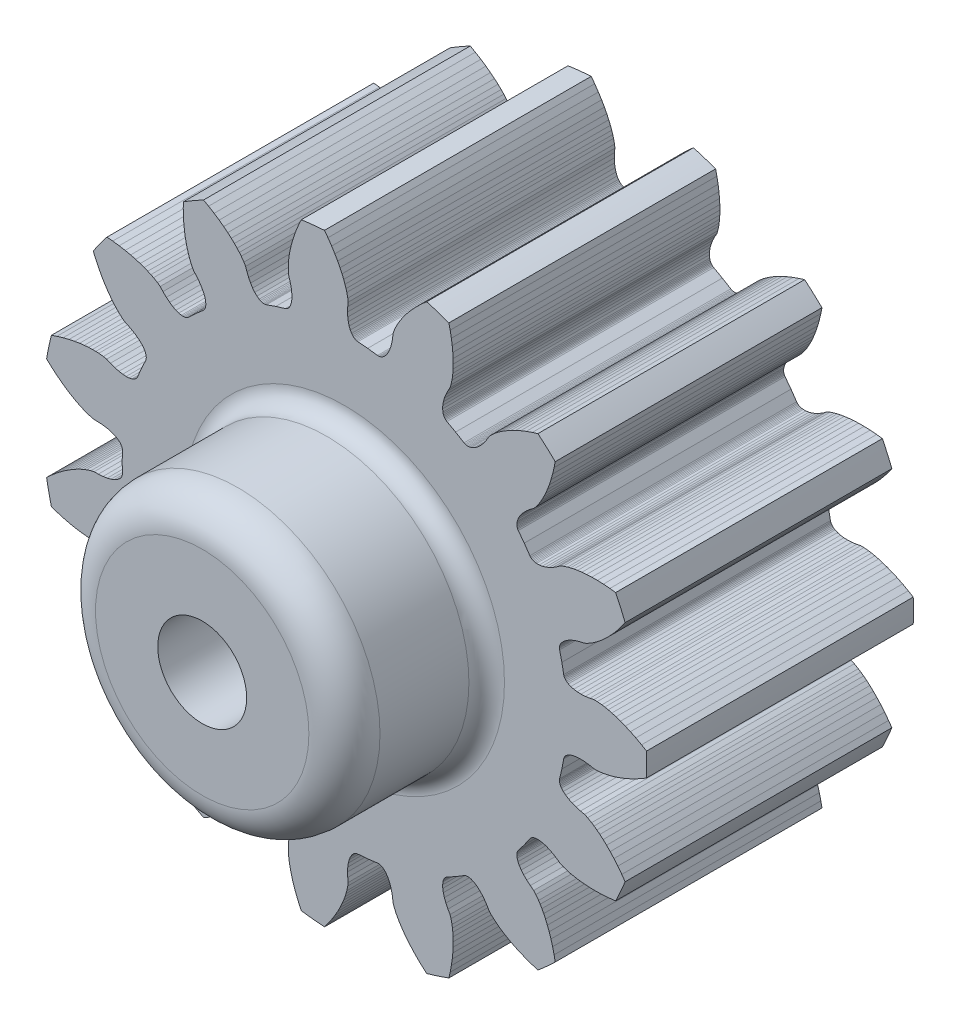
SolidWorks part; units mm, degrees
ref_plane "Front Plane" through (0, 0, 0) normal (0, 0, 1) x (1, 0, 0)
ref_plane "Top Plane" through (0, 0, 0) normal (0, 1, 0) x (1, 0, 0)
ref_plane "Right Plane" through (0, 0, 0) normal (1, 0, 0) x (0, 0, -1)
sketch "Sketch1" plane through (0, 0, 0) normal (0, 0, 1) x (1, 0, 0)
  line L0 (75.5976, 6.0436) -> (75.3755, 5.7533)
  line L1 (75.3755, 5.7533) -> (75.1578, 5.4923)
  line L2 (75.1578, 5.4923) -> (74.945, 5.2579)
  line L3 (74.945, 5.2579) -> (74.7411, 5.0514)
  line L4 (74.7411, 5.0514) -> (74.547, 4.8706)
  line L5 (74.547, 4.8706) -> (74.3629, 4.7129)
  line L6 (74.3629, 4.7129) -> (74.1941, 4.5802)
  line L7 (74.1941, 4.5802) -> (74.0385, 4.4681)
  line L8 (74.0385, 4.4681) -> (73.8985, 4.3758)
  line L9 (73.8985, 4.3758) -> (73.673, 4.2461)
  line L10 (73.673, 4.2461) -> (73.5054, 4.1687)
  line L11 (73.5054, 4.1687) -> (73.2759, 4.1194)
  line L12 (73.2759, 4.1194) -> (73.0228, 4.0472)
  line L13 (73.0228, 4.0472) -> (72.7991, 3.9621)
  line L14 (72.7991, 3.9621) -> (72.6055, 3.8665)
  line L15 (72.6055, 3.8665) -> (72.4424, 3.7627)
  line L16 (72.4424, 3.7627) -> (72.3101, 3.6532)
  line L17 (72.3101, 3.6532) -> (72.2087, 3.5403)
  line L18 (72.2087, 3.5403) -> (72.1697, 3.4833)
  line L19 (72.1697, 3.4833) -> (72.1383, 3.4264)
  line L20 (72.1383, 3.4264) -> (72.1147, 3.3698)
  line L21 (72.1147, 3.3698) -> (72.0987, 3.3139)
  line L22 (72.0987, 3.3139) -> (72.0903, 3.2589)
  line L23 (72.0903, 3.2589) -> (72.0896, 3.2051)
  line L24 (72.0896, 3.2051) -> (72.0992, 3.1402)
  line L25 (72.0992, 3.1402) -> (72.2268, 2.5989)
  line L26 (72.2268, 2.5989) -> (72.3304, 2.0525)
  line L27 (72.3304, 2.0525) -> (72.348, 1.9892)
  line L28 (72.348, 1.9892) -> (72.3706, 1.9404)
  line L29 (72.3706, 1.9404) -> (72.4006, 1.8936)
  line L30 (72.4006, 1.8936) -> (72.4379, 1.849)
  line L31 (72.4379, 1.849) -> (72.4825, 1.807)
  line L32 (72.4825, 1.807) -> (72.5343, 1.7677)
  line L33 (72.5343, 1.7677) -> (72.5932, 1.7315)
  line L34 (72.5932, 1.7315) -> (72.7317, 1.6696)
  line L35 (72.7317, 1.6696) -> (72.8972, 1.6234)
  line L36 (72.8972, 1.6234) -> (73.0884, 1.5949)
  line L37 (73.0884, 1.5949) -> (73.3041, 1.5863)
  line L38 (73.3041, 1.5863) -> (73.543, 1.5995)
  line L39 (73.543, 1.5995) -> (73.8036, 1.6365)
  line L40 (73.8036, 1.6365) -> (74.0333, 1.6849)
  line L41 (74.0333, 1.6849) -> (74.218, 1.6823)
  line L42 (74.218, 1.6823) -> (74.4767, 1.6556)
  line L43 (74.4767, 1.6556) -> (74.6422, 1.6282)
  line L44 (74.6422, 1.6282) -> (74.8299, 1.589)
  line L45 (74.8299, 1.589) -> (75.0381, 1.5364)
  line L46 (75.0381, 1.5364) -> (75.2704, 1.4673)
  line L47 (75.2704, 1.4673) -> (75.5213, 1.3811)
  line L48 (75.5213, 1.3811) -> (75.7915, 1.2753)
  line L49 (75.7915, 1.2753) -> (76.0812, 1.1478)
  line L50 (76.0812, 1.1478) -> (76.3863, 0.9979)
  line L51 (76.3863, 0.9979) -> (76.7073, 0.8231)
  line L52 (76.7073, 0.8231) -> (76.9873, 0.656)
  line L53 (76.9873, -0.656) -> (76.7073, -0.8231)
  line L54 (76.7073, -0.8231) -> (76.3863, -0.9979)
  line L55 (76.3863, -0.9979) -> (76.0812, -1.1478)
  line L56 (76.0812, -1.1478) -> (75.7915, -1.2753)
  line L57 (75.7915, -1.2753) -> (75.5213, -1.3811)
  line L58 (75.5213, -1.3811) -> (75.2704, -1.4673)
  line L59 (75.2704, -1.4673) -> (75.0381, -1.5364)
  line L60 (75.0381, -1.5364) -> (74.8299, -1.589)
  line L61 (74.8299, -1.589) -> (74.6422, -1.6282)
  line L62 (74.6422, -1.6282) -> (74.4767, -1.6556)
  line L63 (74.4767, -1.6556) -> (74.218, -1.6823)
  line L64 (74.218, -1.6823) -> (74.0333, -1.6849)
  line L65 (74.0333, -1.6849) -> (73.8036, -1.6365)
  line L66 (73.8036, -1.6365) -> (73.543, -1.5995)
  line L67 (73.543, -1.5995) -> (73.3041, -1.5863)
  line L68 (73.3041, -1.5863) -> (73.0884, -1.5949)
  line L69 (73.0884, -1.5949) -> (72.8972, -1.6234)
  line L70 (72.8972, -1.6234) -> (72.7317, -1.6696)
  line L71 (72.7317, -1.6696) -> (72.5932, -1.7315)
  line L72 (72.5932, -1.7315) -> (72.5343, -1.7677)
  line L73 (72.5343, -1.7677) -> (72.4825, -1.807)
  line L74 (72.4825, -1.807) -> (72.4379, -1.849)
  line L75 (72.4379, -1.849) -> (72.4006, -1.8936)
  line L76 (72.4006, -1.8936) -> (72.3706, -1.9404)
  line L77 (72.3706, -1.9404) -> (72.348, -1.9892)
  line L78 (72.348, -1.9892) -> (72.3304, -2.0525)
  line L79 (72.3304, -2.0525) -> (72.2268, -2.5989)
  line L80 (72.2268, -2.5989) -> (72.0992, -3.1402)
  line L81 (72.0992, -3.1402) -> (72.0896, -3.2051)
  line L82 (72.0896, -3.2051) -> (72.0903, -3.2589)
  line L83 (72.0903, -3.2589) -> (72.0987, -3.3139)
  line L84 (72.0987, -3.3139) -> (72.1147, -3.3698)
  line L85 (72.1147, -3.3698) -> (72.1383, -3.4264)
  line L86 (72.1383, -3.4264) -> (72.1697, -3.4833)
  line L87 (72.1697, -3.4833) -> (72.2087, -3.5403)
  line L88 (72.2087, -3.5403) -> (72.3101, -3.6532)
  line L89 (72.3101, -3.6532) -> (72.4424, -3.7627)
  line L90 (72.4424, -3.7627) -> (72.6055, -3.8665)
  line L91 (72.6055, -3.8665) -> (72.7991, -3.9621)
  line L92 (72.7991, -3.9621) -> (73.0228, -4.0472)
  line L93 (73.0228, -4.0472) -> (73.2759, -4.1194)
  line L94 (73.2759, -4.1194) -> (73.5054, -4.1687)
  line L95 (73.5054, -4.1687) -> (73.673, -4.2461)
  line L96 (73.673, -4.2461) -> (73.8985, -4.3758)
  line L97 (73.8985, -4.3758) -> (74.0385, -4.4681)
  line L98 (74.0385, -4.4681) -> (74.1941, -4.5802)
  line L99 (74.1941, -4.5802) -> (74.3629, -4.7129)
  line L100 (74.3629, -4.7129) -> (74.547, -4.8706)
  line L101 (74.547, -4.8706) -> (74.7411, -5.0514)
  line L102 (74.7411, -5.0514) -> (74.945, -5.2579)
  line L103 (74.945, -5.2579) -> (75.1578, -5.4923)
  line L104 (75.1578, -5.4923) -> (75.3755, -5.7533)
  line L105 (75.3755, -5.7533) -> (75.5976, -6.0436)
  line L106 (75.5976, -6.0436) -> (75.7855, -6.3101)
  line L107 (75.2519, -7.5086) -> (74.9281, -7.5474)
  line L108 (74.9281, -7.5474) -> (74.5638, -7.5765)
  line L109 (74.5638, -7.5765) -> (74.2241, -7.5894)
  line L110 (74.2241, -7.5894) -> (73.9075, -7.5881)
  line L111 (73.9075, -7.5881) -> (73.6176, -7.5747)
  line L112 (73.6176, -7.5747) -> (73.3534, -7.5515)
  line L113 (73.3534, -7.5515) -> (73.1131, -7.5202)
  line L114 (73.1131, -7.5202) -> (72.9015, -7.4835)
  line L115 (72.9015, -7.4835) -> (72.714, -7.443)
  line L116 (72.714, -7.443) -> (72.5518, -7.4007)
  line L117 (72.5518, -7.4007) -> (72.3045, -7.3199)
  line L118 (72.3045, -7.3199) -> (72.1348, -7.2471)
  line L119 (72.1348, -7.2471) -> (71.9446, -7.1095)
  line L120 (71.9446, -7.1095) -> (71.7216, -6.9697)
  line L121 (71.7216, -6.9697) -> (71.5087, -6.8604)
  line L122 (71.5087, -6.8604) -> (71.3081, -6.7805)
  line L123 (71.3081, -6.7805) -> (71.1219, -6.7288)
  line L124 (71.1219, -6.7288) -> (70.9519, -6.7037)
  line L125 (70.9519, -6.7037) -> (70.8002, -6.704)
  line L126 (70.8002, -6.704) -> (70.7317, -6.713)
  line L127 (70.7317, -6.713) -> (70.6684, -6.7278)
  line L128 (70.6684, -6.7278) -> (70.6105, -6.7481)
  line L129 (70.6105, -6.7481) -> (70.5583, -6.7737)
  line L130 (70.5583, -6.7737) -> (70.5118, -6.8043)
  line L131 (70.5118, -6.8043) -> (70.4714, -6.8396)
  line L132 (70.4714, -6.8396) -> (70.4295, -6.8903)
  line L133 (70.4295, -6.8903) -> (70.1127, -7.3473)
  line L134 (70.1127, -7.3473) -> (69.7759, -7.7899)
  line L135 (69.7759, -7.7899) -> (69.7407, -7.8453)
  line L136 (69.7407, -7.8453) -> (69.7196, -7.8947)
  line L137 (69.7196, -7.8947) -> (69.7048, -7.9484)
  line L138 (69.7048, -7.9484) -> (69.6967, -8.0059)
  line L139 (69.6967, -8.0059) -> (69.6953, -8.0672)
  line L140 (69.6953, -8.0672) -> (69.7008, -8.132)
  line L141 (69.7008, -8.132) -> (69.7133, -8.2)
  line L142 (69.7133, -8.2) -> (69.76, -8.3443)
  line L143 (69.76, -8.3443) -> (69.8363, -8.4982)
  line L144 (69.8363, -8.4982) -> (69.9431, -8.6594)
  line L145 (69.9431, -8.6594) -> (70.081, -8.8254)
  line L146 (70.081, -8.8254) -> (70.2507, -8.9941)
  line L147 (70.2507, -8.9941) -> (70.4526, -9.163)
  line L148 (70.4526, -9.163) -> (70.6422, -9.3014)
  line L149 (70.6422, -9.3014) -> (70.7639, -9.4403)
  line L150 (70.7639, -9.4403) -> (70.9172, -9.6505)
  line L151 (70.9172, -9.6505) -> (71.0075, -9.7918)
  line L152 (71.0075, -9.7918) -> (71.104, -9.9575)
  line L153 (71.104, -9.9575) -> (71.2043, -10.1474)
  line L154 (71.2043, -10.1474) -> (71.3083, -10.3663)
  line L155 (71.3083, -10.3663) -> (71.4121, -10.6104)
  line L156 (71.4121, -10.6104) -> (71.5144, -10.882)
  line L157 (71.5144, -10.882) -> (71.6134, -11.1827)
  line L158 (71.6134, -11.1827) -> (71.7061, -11.5097)
  line L159 (71.7061, -11.5097) -> (71.791, -11.8652)
  line L160 (71.791, -11.8652) -> (71.8542, -12.1851)
  line L161 (70.8792, -13.063) -> (70.5677, -12.9667)
  line L162 (70.5677, -12.9667) -> (70.223, -12.8451)
  line L163 (70.223, -12.8451) -> (69.9075, -12.7187)
  line L164 (69.9075, -12.7187) -> (69.6188, -12.5888)
  line L165 (69.6188, -12.5888) -> (69.3594, -12.4587)
  line L166 (69.3594, -12.4587) -> (69.1275, -12.33)
  line L167 (69.1275, -12.33) -> (68.9207, -12.2036)
  line L168 (68.9207, -12.2036) -> (68.7423, -12.0841)
  line L169 (68.7423, -12.0841) -> (68.5875, -11.9707)
  line L170 (68.5875, -11.9707) -> (68.4565, -11.8661)
  line L171 (68.4565, -11.8661) -> (68.2635, -11.6917)
  line L172 (68.2635, -11.6917) -> (68.138, -11.5562)
  line L173 (68.138, -11.5562) -> (68.0202, -11.3531)
  line L174 (68.0202, -11.3531) -> (67.8734, -11.1347)
  line L175 (67.8734, -11.1347) -> (67.7233, -10.9483)
  line L176 (67.7233, -10.9483) -> (67.5726, -10.7938)
  line L177 (67.5726, -10.7938) -> (67.4235, -10.6707)
  line L178 (67.4235, -10.6707) -> (67.2784, -10.5787)
  line L179 (67.2784, -10.5787) -> (67.1397, -10.5172)
  line L180 (67.1397, -10.5172) -> (67.0735, -10.4976)
  line L181 (67.0735, -10.4976) -> (67.0096, -10.4854)
  line L182 (67.0096, -10.4854) -> (66.9485, -10.4804)
  line L183 (66.9485, -10.4804) -> (66.8904, -10.4825)
  line L184 (66.8904, -10.4825) -> (66.8355, -10.4915)
  line L185 (66.8355, -10.4915) -> (66.7842, -10.5074)
  line L186 (66.7842, -10.5074) -> (66.7253, -10.5367)
  line L187 (66.7253, -10.5367) -> (66.25, -10.8253)
  line L188 (66.25, -10.8253) -> (65.7624, -11.0926)
  line L189 (65.7624, -11.0926) -> (65.7076, -11.129)
  line L190 (65.7076, -11.129) -> (65.6682, -11.1655)
  line L191 (65.6682, -11.1655) -> (65.6329, -11.2085)
  line L192 (65.6329, -11.2085) -> (65.602, -11.2578)
  line L193 (65.602, -11.2578) -> (65.5758, -11.3132)
  line L194 (65.5758, -11.3132) -> (65.5545, -11.3746)
  line L195 (65.5545, -11.3746) -> (65.5383, -11.4418)
  line L196 (65.5383, -11.4418) -> (65.5222, -11.5927)
  line L197 (65.5222, -11.5927) -> (65.5293, -11.7643)
  line L198 (65.5293, -11.7643) -> (65.5614, -11.9549)
  line L199 (65.5614, -11.9549) -> (65.6199, -12.1628)
  line L200 (65.6199, -12.1628) -> (65.7063, -12.3859)
  line L201 (65.7063, -12.3859) -> (65.822, -12.6223)
  line L202 (65.822, -12.6223) -> (65.9389, -12.8259)
  line L203 (65.9389, -12.8259) -> (65.9936, -13.0022)
  line L204 (65.9936, -13.0022) -> (66.0481, -13.2566)
  line L205 (66.0481, -13.2566) -> (66.0732, -13.4224)
  line L206 (66.0732, -13.4224) -> (66.094, -13.6131)
  line L207 (66.094, -13.6131) -> (66.1083, -13.8273)
  line L208 (66.1083, -13.8273) -> (66.1143, -14.0696)
  line L209 (66.1143, -14.0696) -> (66.1098, -14.3348)
  line L210 (66.1098, -14.3348) -> (66.0928, -14.6245)
  line L211 (66.0928, -14.6245) -> (66.061, -14.9395)
  line L212 (66.061, -14.9395) -> (66.0127, -15.2759)
  line L213 (66.0127, -15.2759) -> (65.9456, -15.6352)
  line L214 (65.9456, -15.6352) -> (65.8732, -15.9532)
  line L215 (64.6255, -16.3586) -> (64.3801, -16.1439)
  line L216 (64.3801, -16.1439) -> (64.1146, -15.8926)
  line L217 (64.1146, -15.8926) -> (63.8778, -15.6488)
  line L218 (63.8778, -15.6488) -> (63.6669, -15.4127)
  line L219 (63.6669, -15.4127) -> (63.4829, -15.1884)
  line L220 (63.4829, -15.1884) -> (63.3233, -14.9765)
  line L221 (63.3233, -14.9765) -> (63.1858, -14.7769)
  line L222 (63.1858, -14.7769) -> (63.0715, -14.5951)
  line L223 (63.0715, -14.5951) -> (62.9762, -14.4287)
  line L224 (62.9762, -14.4287) -> (62.899, -14.2798)
  line L225 (62.899, -14.2798) -> (62.7936, -14.042)
  line L226 (62.7936, -14.042) -> (62.7341, -13.8671)
  line L227 (62.7341, -13.8671) -> (62.7091, -13.6337)
  line L228 (62.7091, -13.6337) -> (62.6638, -13.3745)
  line L229 (62.6638, -13.3745) -> (62.6025, -13.1432)
  line L230 (62.6025, -13.1432) -> (62.5277, -12.9406)
  line L231 (62.5277, -12.9406) -> (62.4415, -12.7676)
  line L232 (62.4415, -12.7676) -> (62.3464, -12.6246)
  line L233 (62.3464, -12.6246) -> (62.2447, -12.5119)
  line L234 (62.2447, -12.5119) -> (62.1921, -12.4671)
  line L235 (62.1921, -12.4671) -> (62.1388, -12.43)
  line L236 (62.1388, -12.43) -> (62.085, -12.4005)
  line L237 (62.085, -12.4005) -> (62.0311, -12.3788)
  line L238 (62.0311, -12.3788) -> (61.9773, -12.3648)
  line L239 (61.9773, -12.3648) -> (61.9239, -12.3584)
  line L240 (61.9239, -12.3584) -> (61.8582, -12.3611)
  line L241 (61.8582, -12.3611) -> (61.3066, -12.4315)
  line L242 (61.3066, -12.4315) -> (60.7524, -12.4774)
  line L243 (60.7524, -12.4774) -> (60.6876, -12.4883)
  line L244 (60.6876, -12.4883) -> (60.6367, -12.5057)
  line L245 (60.6367, -12.5057) -> (60.587, -12.5306)
  line L246 (60.587, -12.5306) -> (60.5388, -12.5631)
  line L247 (60.5388, -12.5631) -> (60.4923, -12.603)
  line L248 (60.4923, -12.603) -> (60.4478, -12.6504)
  line L249 (60.4478, -12.6504) -> (60.4057, -12.7052)
  line L250 (60.4057, -12.7052) -> (60.3296, -12.8365)
  line L251 (60.3296, -12.8365) -> (60.2663, -12.9962)
  line L252 (60.2663, -12.9962) -> (60.2181, -13.1834)
  line L253 (60.2181, -13.1834) -> (60.1869, -13.397)
  line L254 (60.1869, -13.397) -> (60.1751, -13.636)
  line L255 (60.1751, -13.636) -> (60.1847, -13.8991)
  line L256 (60.1847, -13.8991) -> (60.2087, -14.1326)
  line L257 (60.2087, -14.1326) -> (60.1869, -14.316)
  line L258 (60.1869, -14.316) -> (60.1333, -14.5705)
  line L259 (60.1333, -14.5705) -> (60.0888, -14.7321)
  line L260 (60.0888, -14.7321) -> (60.0302, -14.9148)
  line L261 (60.0302, -14.9148) -> (59.9561, -15.1163)
  line L262 (59.9561, -15.1163) -> (59.8631, -15.3401)
  line L263 (59.8631, -15.3401) -> (59.7511, -15.5806)
  line L264 (59.7511, -15.5806) -> (59.6177, -15.8383)
  line L265 (59.6177, -15.8383) -> (59.4605, -16.1131)
  line L266 (59.4605, -16.1131) -> (59.2796, -16.4008)
  line L267 (59.2796, -16.4008) -> (59.0722, -16.7018)
  line L268 (59.0722, -16.7018) -> (58.8767, -16.9628)
  line L269 (57.572, -16.8257) -> (57.4351, -16.5297)
  line L270 (57.4351, -16.5297) -> (57.2948, -16.1922)
  line L271 (57.2948, -16.1922) -> (57.1776, -15.8731)
  line L272 (57.1776, -15.8731) -> (57.081, -15.5717)
  line L273 (57.081, -15.5717) -> (57.0041, -15.2919)
  line L274 (57.0041, -15.2919) -> (56.9445, -15.0334)
  line L275 (56.9445, -15.0334) -> (56.9001, -14.7951)
  line L276 (56.9001, -14.7951) -> (56.8695, -14.5826)
  line L277 (56.8695, -14.5826) -> (56.8502, -14.3918)
  line L278 (56.8502, -14.3918) -> (56.8403, -14.2244)
  line L279 (56.8403, -14.2244) -> (56.8407, -13.9642)
  line L280 (56.8407, -13.9642) -> (56.8575, -13.7804)
  line L281 (56.8575, -13.7804) -> (56.9296, -13.5569)
  line L282 (56.9296, -13.5569) -> (56.9936, -13.3016)
  line L283 (56.9936, -13.3016) -> (57.0317, -13.0654)
  line L284 (57.0317, -13.0654) -> (57.0457, -12.85)
  line L285 (57.0457, -12.85) -> (57.0374, -12.6568)
  line L286 (57.0374, -12.6568) -> (57.0087, -12.4875)
  line L287 (57.0087, -12.4875) -> (56.9616, -12.3432)
  line L288 (56.9616, -12.3432) -> (56.9318, -12.2809)
  line L289 (56.9318, -12.2809) -> (56.8982, -12.2253)
  line L290 (56.8982, -12.2253) -> (56.861, -12.1765)
  line L291 (56.861, -12.1765) -> (56.8206, -12.1347)
  line L292 (56.8206, -12.1347) -> (56.7771, -12.1)
  line L293 (56.7771, -12.1) -> (56.7309, -12.0725)
  line L294 (56.7309, -12.0725) -> (56.6699, -12.0483)
  line L295 (56.6699, -12.0483) -> (56.1373, -11.8882)
  line L296 (56.1373, -11.8882) -> (55.6123, -11.7047)
  line L297 (55.6123, -11.7047) -> (55.5487, -11.6883)
  line L298 (55.5487, -11.6883) -> (55.4952, -11.6835)
  line L299 (55.4952, -11.6835) -> (55.4396, -11.686)
  line L300 (55.4396, -11.686) -> (55.3823, -11.6961)
  line L301 (55.3823, -11.6961) -> (55.3236, -11.7137)
  line L302 (55.3236, -11.7137) -> (55.2637, -11.7389)
  line L303 (55.2637, -11.7389) -> (55.2029, -11.7718)
  line L304 (55.2029, -11.7718) -> (55.0801, -11.8608)
  line L305 (55.0801, -11.8608) -> (54.9573, -11.981)
  line L306 (54.9573, -11.981) -> (54.837, -12.1323)
  line L307 (54.837, -12.1323) -> (54.7217, -12.3149)
  line L308 (54.7217, -12.3149) -> (54.6137, -12.5284)
  line L309 (54.6137, -12.5284) -> (54.5155, -12.7725)
  line L310 (54.5155, -12.7725) -> (54.4425, -12.9957)
  line L311 (54.4425, -12.9957) -> (54.348, -13.1543)
  line L312 (54.348, -13.1543) -> (54.1954, -13.365)
  line L313 (54.1954, -13.365) -> (54.089, -13.4946)
  line L314 (54.089, -13.4946) -> (53.9612, -13.6376)
  line L315 (53.9612, -13.6376) -> (53.8115, -13.7916)
  line L316 (53.8115, -13.7916) -> (53.6355, -13.9582)
  line L317 (53.6355, -13.9582) -> (53.4354, -14.1323)
  line L318 (53.4354, -14.1323) -> (53.2087, -14.3135)
  line L319 (53.2087, -14.3135) -> (52.9534, -14.5006)
  line L320 (52.9534, -14.5006) -> (52.671, -14.6899)
  line L321 (52.671, -14.6899) -> (52.3592, -14.8805)
  line L322 (52.3592, -14.8805) -> (52.0744, -15.0394)
  line L323 (50.9383, -14.3834) -> (50.9336, -14.0574)
  line L324 (50.9336, -14.0574) -> (50.9427, -13.692)
  line L325 (50.9427, -13.692) -> (50.9654, -13.3528)
  line L326 (50.9654, -13.3528) -> (50.9998, -13.0382)
  line L327 (50.9998, -13.0382) -> (51.0433, -12.7513)
  line L328 (51.0433, -12.7513) -> (51.0941, -12.4909)
  line L329 (51.0941, -12.4909) -> (51.1504, -12.2552)
  line L330 (51.1504, -12.2552) -> (51.2089, -12.0486)
  line L331 (51.2089, -12.0486) -> (51.2688, -11.8664)
  line L332 (51.2688, -11.8664) -> (51.3279, -11.7094)
  line L333 (51.3279, -11.7094) -> (51.4341, -11.472)
  line L334 (51.4341, -11.472) -> (51.5242, -11.3108)
  line L335 (51.5242, -11.3108) -> (51.6809, -11.136)
  line L336 (51.6809, -11.136) -> (51.8432, -10.9288)
  line L337 (51.8432, -10.9288) -> (51.9742, -10.7286)
  line L338 (51.9742, -10.7286) -> (52.0746, -10.5374)
  line L339 (52.0746, -10.5374) -> (52.1455, -10.3576)
  line L340 (52.1455, -10.3576) -> (52.1882, -10.1912)
  line L341 (52.1882, -10.1912) -> (52.2038, -10.0403)
  line L342 (52.2038, -10.0403) -> (52.202, -9.9712)
  line L343 (52.202, -9.9712) -> (52.1939, -9.9067)
  line L344 (52.1939, -9.9067) -> (52.1797, -9.847)
  line L345 (52.1797, -9.847) -> (52.1598, -9.7924)
  line L346 (52.1598, -9.7924) -> (52.1342, -9.743)
  line L347 (52.1342, -9.743) -> (52.1033, -9.6991)
  line L348 (52.1033, -9.6991) -> (52.0573, -9.6522)
  line L349 (52.0573, -9.6522) -> (51.6359, -9.2893)
  line L350 (51.6359, -9.2893) -> (51.231, -8.9081)
  line L351 (51.231, -8.9081) -> (51.1795, -8.8673)
  line L352 (51.1795, -8.8673) -> (51.1325, -8.8411)
  line L353 (51.1325, -8.8411) -> (51.0808, -8.8208)
  line L354 (51.0808, -8.8208) -> (51.0243, -8.8067)
  line L355 (51.0243, -8.8067) -> (50.9635, -8.7989)
  line L356 (50.9635, -8.7989) -> (50.8985, -8.7976)
  line L357 (50.8985, -8.7976) -> (50.8297, -8.8029)
  line L358 (50.8297, -8.8029) -> (50.6812, -8.8343)
  line L359 (50.6812, -8.8343) -> (50.5202, -8.8941)
  line L360 (50.5202, -8.8941) -> (50.3487, -8.9835)
  line L361 (50.3487, -8.9835) -> (50.1691, -9.1033)
  line L362 (50.1691, -9.1033) -> (49.9836, -9.2544)
  line L363 (49.9836, -9.2544) -> (49.7946, -9.4375)
  line L364 (49.7946, -9.4375) -> (49.6371, -9.6117)
  line L365 (49.6371, -9.6117) -> (49.4863, -9.7182)
  line L366 (49.4863, -9.7182) -> (49.2612, -9.8486)
  line L367 (49.2612, -9.8486) -> (49.1113, -9.9237)
  line L368 (49.1113, -9.9237) -> (48.9363, -10.0024)
  line L369 (48.9363, -10.0024) -> (48.737, -10.0822)
  line L370 (48.737, -10.0822) -> (48.5084, -10.1628)
  line L371 (48.5084, -10.1628) -> (48.2548, -10.2405)
  line L372 (48.2548, -10.2405) -> (47.974, -10.3138)
  line L373 (47.974, -10.3138) -> (47.6647, -10.3809)
  line L374 (47.6647, -10.3809) -> (47.3297, -10.4389)
  line L375 (47.3297, -10.4389) -> (46.9673, -10.4862)
  line L376 (46.9673, -10.4862) -> (46.6426, -10.5156)
  line L377 (45.8714, -9.4542) -> (45.9997, -9.1544)
  line L378 (45.9997, -9.1544) -> (46.1567, -8.8243)
  line L379 (46.1567, -8.8243) -> (46.3154, -8.5237)
  line L380 (46.3154, -8.5237) -> (46.4748, -8.2502)
  line L381 (46.4748, -8.2502) -> (46.6313, -8.0059)
  line L382 (46.6313, -8.0059) -> (46.7835, -7.7886)
  line L383 (46.7835, -7.7886) -> (46.9308, -7.5962)
  line L384 (46.9308, -7.5962) -> (47.0683, -7.4313)
  line L385 (47.0683, -7.4313) -> (47.1972, -7.2892)
  line L386 (47.1972, -7.2892) -> (47.315, -7.1698)
  line L387 (47.315, -7.1698) -> (47.5086, -6.9961)
  line L388 (47.5086, -6.9961) -> (47.6565, -6.8855)
  line L389 (47.6565, -6.8855) -> (47.8707, -6.7896)
  line L390 (47.8707, -6.7896) -> (48.1033, -6.6663)
  line L391 (48.1033, -6.6663) -> (48.3043, -6.5366)
  line L392 (48.3043, -6.5366) -> (48.4738, -6.4029)
  line L393 (48.4738, -6.4029) -> (48.6118, -6.2674)
  line L394 (48.6118, -6.2674) -> (48.7184, -6.1328)
  line L395 (48.7184, -6.1328) -> (48.7941, -6.0013)
  line L396 (48.7941, -6.0013) -> (48.8205, -5.9374)
  line L397 (48.8205, -5.9374) -> (48.8393, -5.8752)
  line L398 (48.8393, -5.8752) -> (48.8507, -5.8149)
  line L399 (48.8507, -5.8149) -> (48.8547, -5.7569)
  line L400 (48.8547, -5.7569) -> (48.8514, -5.7014)
  line L401 (48.8514, -5.7014) -> (48.841, -5.6487)
  line L402 (48.841, -5.6487) -> (48.8181, -5.5871)
  line L403 (48.8181, -5.5871) -> (48.5807, -5.0842)
  line L404 (48.5807, -5.0842) -> (48.3658, -4.5713)
  line L405 (48.3658, -4.5713) -> (48.3354, -4.5131)
  line L406 (48.3354, -4.5131) -> (48.3032, -4.47)
  line L407 (48.3032, -4.47) -> (48.2641, -4.4305)
  line L408 (48.2641, -4.4305) -> (48.2183, -4.3946)
  line L409 (48.2183, -4.3946) -> (48.1659, -4.3627)
  line L410 (48.1659, -4.3627) -> (48.1071, -4.3351)
  line L411 (48.1071, -4.3351) -> (48.042, -4.312)
  line L412 (48.042, -4.312) -> (47.8936, -4.2802)
  line L413 (47.8936, -4.2802) -> (47.7222, -4.2694)
  line L414 (47.7222, -4.2694) -> (47.5292, -4.2813)
  line L415 (47.5292, -4.2813) -> (47.3164, -4.3177)
  line L416 (47.3164, -4.3177) -> (47.0855, -4.3803)
  line L417 (47.0855, -4.3803) -> (46.8383, -4.4707)
  line L418 (46.8383, -4.4707) -> (46.6236, -4.5657)
  line L419 (46.6236, -4.5657) -> (46.4425, -4.6017)
  line L420 (46.4425, -4.6017) -> (46.1838, -4.6293)
  line L421 (46.1838, -4.6293) -> (46.0163, -4.6369)
  line L422 (46.0163, -4.6369) -> (45.8245, -4.6376)
  line L423 (45.8245, -4.6376) -> (45.6099, -4.6295)
  line L424 (45.6099, -4.6295) -> (45.3684, -4.6101)
  line L425 (45.3684, -4.6101) -> (45.1051, -4.5779)
  line L426 (45.1051, -4.5779) -> (44.8187, -4.5307)
  line L427 (44.8187, -4.5307) -> (44.5088, -4.4662)
  line L428 (44.5088, -4.4662) -> (44.1793, -4.3829)
  line L429 (44.1793, -4.3829) -> (43.8289, -4.2787)
  line L430 (43.8289, -4.2787) -> (43.5203, -4.1735)
  line L431 (43.2475, -2.8902) -> (43.4867, -2.6686)
  line L432 (43.4867, -2.6686) -> (43.7643, -2.4308)
  line L433 (43.7643, -2.4308) -> (44.0316, -2.2208)
  line L434 (44.0316, -2.2208) -> (44.2884, -2.0358)
  line L435 (44.2884, -2.0358) -> (44.5308, -1.8762)
  line L436 (44.5308, -1.8762) -> (44.7582, -1.7396)
  line L437 (44.7582, -1.7396) -> (44.9711, -1.6237)
  line L438 (44.9711, -1.6237) -> (45.1638, -1.529)
  line L439 (45.1638, -1.529) -> (45.3393, -1.4516)
  line L440 (45.3393, -1.4516) -> (45.4954, -1.3905)
  line L441 (45.4954, -1.3905) -> (45.7429, -1.3105)
  line L442 (45.7429, -1.3105) -> (45.923, -1.2697)
  line L443 (45.923, -1.2697) -> (46.1578, -1.2692)
  line L444 (46.1578, -1.2692) -> (46.4204, -1.2512)
  line L445 (46.4204, -1.2512) -> (46.6568, -1.2145)
  line L446 (46.6568, -1.2145) -> (46.866, -1.1612)
  line L447 (46.866, -1.1612) -> (47.0472, -1.0936)
  line L448 (47.0472, -1.0936) -> (47.1993, -1.0139)
  line L449 (47.1993, -1.0139) -> (47.322, -0.9246)
  line L450 (47.322, -0.9246) -> (47.3721, -0.877)
  line L451 (47.3721, -0.877) -> (47.4145, -0.8278)
  line L452 (47.4145, -0.8278) -> (47.4494, -0.7774)
  line L453 (47.4494, -0.7774) -> (47.4767, -0.726)
  line L454 (47.4767, -0.726) -> (47.4963, -0.674)
  line L455 (47.4963, -0.674) -> (47.5082, -0.6215)
  line L456 (47.5082, -0.6215) -> (47.5123, -0.556)
  line L457 (47.5123, -0.556) -> (47.5, 0)
  line L458 (47.5, 0) -> (47.5123, 0.556)
  line L459 (47.5123, 0.556) -> (47.5082, 0.6215)
  line L460 (47.5082, 0.6215) -> (47.4963, 0.674)
  line L461 (47.4963, 0.674) -> (47.4767, 0.726)
  line L462 (47.4767, 0.726) -> (47.4494, 0.7774)
  line L463 (47.4494, 0.7774) -> (47.4145, 0.8278)
  line L464 (47.4145, 0.8278) -> (47.3721, 0.877)
  line L465 (47.3721, 0.877) -> (47.322, 0.9246)
  line L466 (47.322, 0.9246) -> (47.1993, 1.0139)
  line L467 (47.1993, 1.0139) -> (47.0472, 1.0936)
  line L468 (47.0472, 1.0936) -> (46.866, 1.1612)
  line L469 (46.866, 1.1612) -> (46.6568, 1.2145)
  line L470 (46.6568, 1.2145) -> (46.4204, 1.2512)
  line L471 (46.4204, 1.2512) -> (46.1578, 1.2692)
  line L472 (46.1578, 1.2692) -> (45.923, 1.2697)
  line L473 (45.923, 1.2697) -> (45.7429, 1.3105)
  line L474 (45.7429, 1.3105) -> (45.4954, 1.3905)
  line L475 (45.4954, 1.3905) -> (45.3393, 1.4516)
  line L476 (45.3393, 1.4516) -> (45.1638, 1.529)
  line L477 (45.1638, 1.529) -> (44.9711, 1.6237)
  line L478 (44.9711, 1.6237) -> (44.7582, 1.7396)
  line L479 (44.7582, 1.7396) -> (44.5308, 1.8762)
  line L480 (44.5308, 1.8762) -> (44.2884, 2.0358)
  line L481 (44.2884, 2.0358) -> (44.0316, 2.2208)
  line L482 (44.0316, 2.2208) -> (43.7643, 2.4308)
  line L483 (43.7643, 2.4308) -> (43.4867, 2.6686)
  line L484 (43.4867, 2.6686) -> (43.2475, 2.8902)
  line L485 (43.5203, 4.1735) -> (43.8289, 4.2787)
  line L486 (43.8289, 4.2787) -> (44.1793, 4.3829)
  line L487 (44.1793, 4.3829) -> (44.5088, 4.4662)
  line L488 (44.5088, 4.4662) -> (44.8187, 4.5307)
  line L489 (44.8187, 4.5307) -> (45.1051, 4.5779)
  line L490 (45.1051, 4.5779) -> (45.3684, 4.6101)
  line L491 (45.3684, 4.6101) -> (45.6099, 4.6295)
  line L492 (45.6099, 4.6295) -> (45.8245, 4.6376)
  line L493 (45.8245, 4.6376) -> (46.0163, 4.6369)
  line L494 (46.0163, 4.6369) -> (46.1838, 4.6293)
  line L495 (46.1838, 4.6293) -> (46.4425, 4.6017)
  line L496 (46.4425, 4.6017) -> (46.6236, 4.5657)
  line L497 (46.6236, 4.5657) -> (46.8383, 4.4707)
  line L498 (46.8383, 4.4707) -> (47.0855, 4.3803)
  line L499 (47.0855, 4.3803) -> (47.3164, 4.3177)
  line L500 (47.3164, 4.3177) -> (47.5292, 4.2813)
  line L501 (47.5292, 4.2813) -> (47.7222, 4.2694)
  line L502 (47.7222, 4.2694) -> (47.8936, 4.2802)
  line L503 (47.8936, 4.2802) -> (48.042, 4.312)
  line L504 (48.042, 4.312) -> (48.1071, 4.3351)
  line L505 (48.1071, 4.3351) -> (48.1659, 4.3627)
  line L506 (48.1659, 4.3627) -> (48.2183, 4.3946)
  line L507 (48.2183, 4.3946) -> (48.2641, 4.4305)
  line L508 (48.2641, 4.4305) -> (48.3032, 4.47)
  line L509 (48.3032, 4.47) -> (48.3354, 4.5131)
  line L510 (48.3354, 4.5131) -> (48.3658, 4.5713)
  line L511 (48.3658, 4.5713) -> (48.5807, 5.0842)
  line L512 (48.5807, 5.0842) -> (48.8181, 5.5871)
  line L513 (48.8181, 5.5871) -> (48.841, 5.6487)
  line L514 (48.841, 5.6487) -> (48.8514, 5.7014)
  line L515 (48.8514, 5.7014) -> (48.8547, 5.7569)
  line L516 (48.8547, 5.7569) -> (48.8507, 5.8149)
  line L517 (48.8507, 5.8149) -> (48.8393, 5.8752)
  line L518 (48.8393, 5.8752) -> (48.8205, 5.9374)
  line L519 (48.8205, 5.9374) -> (48.7941, 6.0013)
  line L520 (48.7941, 6.0013) -> (48.7184, 6.1328)
  line L521 (48.7184, 6.1328) -> (48.6118, 6.2674)
  line L522 (48.6118, 6.2674) -> (48.4738, 6.4029)
  line L523 (48.4738, 6.4029) -> (48.3043, 6.5366)
  line L524 (48.3043, 6.5366) -> (48.1033, 6.6663)
  line L525 (48.1033, 6.6663) -> (47.8707, 6.7896)
  line L526 (47.8707, 6.7896) -> (47.6565, 6.8855)
  line L527 (47.6565, 6.8855) -> (47.5086, 6.9961)
  line L528 (47.5086, 6.9961) -> (47.315, 7.1698)
  line L529 (47.315, 7.1698) -> (47.1972, 7.2892)
  line L530 (47.1972, 7.2892) -> (47.0683, 7.4313)
  line L531 (47.0683, 7.4313) -> (46.9308, 7.5962)
  line L532 (46.9308, 7.5962) -> (46.7835, 7.7886)
  line L533 (46.7835, 7.7886) -> (46.6313, 8.0059)
  line L534 (46.6313, 8.0059) -> (46.4748, 8.2502)
  line L535 (46.4748, 8.2502) -> (46.3154, 8.5237)
  line L536 (46.3154, 8.5237) -> (46.1567, 8.8243)
  line L537 (46.1567, 8.8243) -> (45.9997, 9.1544)
  line L538 (45.9997, 9.1544) -> (45.8714, 9.4542)
  line L539 (46.6426, 10.5156) -> (46.9673, 10.4862)
  line L540 (46.9673, 10.4862) -> (47.3297, 10.4389)
  line L541 (47.3297, 10.4389) -> (47.6647, 10.3809)
  line L542 (47.6647, 10.3809) -> (47.974, 10.3138)
  line L543 (47.974, 10.3138) -> (48.2548, 10.2405)
  line L544 (48.2548, 10.2405) -> (48.5084, 10.1628)
  line L545 (48.5084, 10.1628) -> (48.737, 10.0822)
  line L546 (48.737, 10.0822) -> (48.9363, 10.0024)
  line L547 (48.9363, 10.0024) -> (49.1113, 9.9237)
  line L548 (49.1113, 9.9237) -> (49.2612, 9.8486)
  line L549 (49.2612, 9.8486) -> (49.4863, 9.7182)
  line L550 (49.4863, 9.7182) -> (49.6371, 9.6117)
  line L551 (49.6371, 9.6117) -> (49.7946, 9.4375)
  line L552 (49.7946, 9.4375) -> (49.9836, 9.2544)
  line L553 (49.9836, 9.2544) -> (50.1691, 9.1033)
  line L554 (50.1691, 9.1033) -> (50.3487, 8.9835)
  line L555 (50.3487, 8.9835) -> (50.5202, 8.8941)
  line L556 (50.5202, 8.8941) -> (50.6812, 8.8343)
  line L557 (50.6812, 8.8343) -> (50.8297, 8.8029)
  line L558 (50.8297, 8.8029) -> (50.8985, 8.7976)
  line L559 (50.8985, 8.7976) -> (50.9635, 8.7989)
  line L560 (50.9635, 8.7989) -> (51.0243, 8.8067)
  line L561 (51.0243, 8.8067) -> (51.0808, 8.8208)
  line L562 (51.0808, 8.8208) -> (51.1325, 8.8411)
  line L563 (51.1325, 8.8411) -> (51.1795, 8.8673)
  line L564 (51.1795, 8.8673) -> (51.231, 8.9081)
  line L565 (51.231, 8.9081) -> (51.6359, 9.2893)
  line L566 (51.6359, 9.2893) -> (52.0573, 9.6522)
  line L567 (52.0573, 9.6522) -> (52.1033, 9.6991)
  line L568 (52.1033, 9.6991) -> (52.1342, 9.743)
  line L569 (52.1342, 9.743) -> (52.1598, 9.7924)
  line L570 (52.1598, 9.7924) -> (52.1797, 9.847)
  line L571 (52.1797, 9.847) -> (52.1939, 9.9067)
  line L572 (52.1939, 9.9067) -> (52.202, 9.9712)
  line L573 (52.202, 9.9712) -> (52.2038, 10.0403)
  line L574 (52.2038, 10.0403) -> (52.1882, 10.1912)
  line L575 (52.1882, 10.1912) -> (52.1455, 10.3576)
  line L576 (52.1455, 10.3576) -> (52.0746, 10.5374)
  line L577 (52.0746, 10.5374) -> (51.9742, 10.7286)
  line L578 (51.9742, 10.7286) -> (51.8432, 10.9288)
  line L579 (51.8432, 10.9288) -> (51.6809, 11.136)
  line L580 (51.6809, 11.136) -> (51.5242, 11.3108)
  line L581 (51.5242, 11.3108) -> (51.4341, 11.472)
  line L582 (51.4341, 11.472) -> (51.3279, 11.7094)
  line L583 (51.3279, 11.7094) -> (51.2688, 11.8664)
  line L584 (51.2688, 11.8664) -> (51.2089, 12.0486)
  line L585 (51.2089, 12.0486) -> (51.1504, 12.2552)
  line L586 (51.1504, 12.2552) -> (51.0941, 12.4909)
  line L587 (51.0941, 12.4909) -> (51.0433, 12.7513)
  line L588 (51.0433, 12.7513) -> (50.9998, 13.0382)
  line L589 (50.9998, 13.0382) -> (50.9654, 13.3528)
  line L590 (50.9654, 13.3528) -> (50.9427, 13.692)
  line L591 (50.9427, 13.692) -> (50.9336, 14.0574)
  line L592 (50.9336, 14.0574) -> (50.9383, 14.3834)
  line L593 (52.0744, 15.0394) -> (52.3592, 14.8805)
  line L594 (52.3592, 14.8805) -> (52.671, 14.6899)
  line L595 (52.671, 14.6899) -> (52.9534, 14.5006)
  line L596 (52.9534, 14.5006) -> (53.2087, 14.3135)
  line L597 (53.2087, 14.3135) -> (53.4354, 14.1323)
  line L598 (53.4354, 14.1323) -> (53.6355, 13.9582)
  line L599 (53.6355, 13.9582) -> (53.8115, 13.7916)
  line L600 (53.8115, 13.7916) -> (53.9612, 13.6376)
  line L601 (53.9612, 13.6376) -> (54.089, 13.4946)
  line L602 (54.089, 13.4946) -> (54.1954, 13.365)
  line L603 (54.1954, 13.365) -> (54.348, 13.1543)
  line L604 (54.348, 13.1543) -> (54.4425, 12.9957)
  line L605 (54.4425, 12.9957) -> (54.5155, 12.7725)
  line L606 (54.5155, 12.7725) -> (54.6137, 12.5284)
  line L607 (54.6137, 12.5284) -> (54.7217, 12.3149)
  line L608 (54.7217, 12.3149) -> (54.837, 12.1323)
  line L609 (54.837, 12.1323) -> (54.9573, 11.981)
  line L610 (54.9573, 11.981) -> (55.0801, 11.8608)
  line L611 (55.0801, 11.8608) -> (55.2029, 11.7718)
  line L612 (55.2029, 11.7718) -> (55.2637, 11.7389)
  line L613 (55.2637, 11.7389) -> (55.3236, 11.7137)
  line L614 (55.3236, 11.7137) -> (55.3823, 11.6961)
  line L615 (55.3823, 11.6961) -> (55.4396, 11.686)
  line L616 (55.4396, 11.686) -> (55.4952, 11.6835)
  line L617 (55.4952, 11.6835) -> (55.5487, 11.6883)
  line L618 (55.5487, 11.6883) -> (55.6123, 11.7047)
  line L619 (55.6123, 11.7047) -> (56.1373, 11.8882)
  line L620 (56.1373, 11.8882) -> (56.6699, 12.0483)
  line L621 (56.6699, 12.0483) -> (56.7309, 12.0725)
  line L622 (56.7309, 12.0725) -> (56.7771, 12.1)
  line L623 (56.7771, 12.1) -> (56.8206, 12.1347)
  line L624 (56.8206, 12.1347) -> (56.861, 12.1765)
  line L625 (56.861, 12.1765) -> (56.8982, 12.2253)
  line L626 (56.8982, 12.2253) -> (56.9318, 12.2809)
  line L627 (56.9318, 12.2809) -> (56.9616, 12.3432)
  line L628 (56.9616, 12.3432) -> (57.0087, 12.4875)
  line L629 (57.0087, 12.4875) -> (57.0374, 12.6568)
  line L630 (57.0374, 12.6568) -> (57.0457, 12.85)
  line L631 (57.0457, 12.85) -> (57.0317, 13.0654)
  line L632 (57.0317, 13.0654) -> (56.9936, 13.3016)
  line L633 (56.9936, 13.3016) -> (56.9296, 13.5569)
  line L634 (56.9296, 13.5569) -> (56.8575, 13.7804)
  line L635 (56.8575, 13.7804) -> (56.8407, 13.9642)
  line L636 (56.8407, 13.9642) -> (56.8403, 14.2244)
  line L637 (56.8403, 14.2244) -> (56.8502, 14.3918)
  line L638 (56.8502, 14.3918) -> (56.8695, 14.5826)
  line L639 (56.8695, 14.5826) -> (56.9001, 14.7951)
  line L640 (56.9001, 14.7951) -> (56.9445, 15.0334)
  line L641 (56.9445, 15.0334) -> (57.0041, 15.2919)
  line L642 (57.0041, 15.2919) -> (57.081, 15.5717)
  line L643 (57.081, 15.5717) -> (57.1776, 15.8731)
  line L644 (57.1776, 15.8731) -> (57.2948, 16.1922)
  line L645 (57.2948, 16.1922) -> (57.4351, 16.5297)
  line L646 (57.4351, 16.5297) -> (57.572, 16.8257)
  line L647 (58.8767, 16.9628) -> (59.0722, 16.7018)
  line L648 (59.0722, 16.7018) -> (59.2796, 16.4008)
  line L649 (59.2796, 16.4008) -> (59.4605, 16.1131)
  line L650 (59.4605, 16.1131) -> (59.6177, 15.8383)
  line L651 (59.6177, 15.8383) -> (59.7511, 15.5806)
  line L652 (59.7511, 15.5806) -> (59.8631, 15.3401)
  line L653 (59.8631, 15.3401) -> (59.9561, 15.1163)
  line L654 (59.9561, 15.1163) -> (60.0302, 14.9148)
  line L655 (60.0302, 14.9148) -> (60.0888, 14.7321)
  line L656 (60.0888, 14.7321) -> (60.1333, 14.5705)
  line L657 (60.1333, 14.5705) -> (60.1869, 14.316)
  line L658 (60.1869, 14.316) -> (60.2087, 14.1326)
  line L659 (60.2087, 14.1326) -> (60.1847, 13.8991)
  line L660 (60.1847, 13.8991) -> (60.1751, 13.636)
  line L661 (60.1751, 13.636) -> (60.1869, 13.397)
  line L662 (60.1869, 13.397) -> (60.2181, 13.1834)
  line L663 (60.2181, 13.1834) -> (60.2663, 12.9962)
  line L664 (60.2663, 12.9962) -> (60.3296, 12.8365)
  line L665 (60.3296, 12.8365) -> (60.4057, 12.7052)
  line L666 (60.4057, 12.7052) -> (60.4478, 12.6504)
  line L667 (60.4478, 12.6504) -> (60.4923, 12.603)
  line L668 (60.4923, 12.603) -> (60.5388, 12.5631)
  line L669 (60.5388, 12.5631) -> (60.587, 12.5306)
  line L670 (60.587, 12.5306) -> (60.6367, 12.5057)
  line L671 (60.6367, 12.5057) -> (60.6876, 12.4883)
  line L672 (60.6876, 12.4883) -> (60.7524, 12.4774)
  line L673 (60.7524, 12.4774) -> (61.3066, 12.4315)
  line L674 (61.3066, 12.4315) -> (61.8582, 12.3611)
  line L675 (61.8582, 12.3611) -> (61.9239, 12.3584)
  line L676 (61.9239, 12.3584) -> (61.9773, 12.3648)
  line L677 (61.9773, 12.3648) -> (62.0311, 12.3788)
  line L678 (62.0311, 12.3788) -> (62.085, 12.4005)
  line L679 (62.085, 12.4005) -> (62.1388, 12.43)
  line L680 (62.1388, 12.43) -> (62.1921, 12.4671)
  line L681 (62.1921, 12.4671) -> (62.2447, 12.5119)
  line L682 (62.2447, 12.5119) -> (62.3464, 12.6246)
  line L683 (62.3464, 12.6246) -> (62.4415, 12.7676)
  line L684 (62.4415, 12.7676) -> (62.5277, 12.9406)
  line L685 (62.5277, 12.9406) -> (62.6025, 13.1432)
  line L686 (62.6025, 13.1432) -> (62.6638, 13.3745)
  line L687 (62.6638, 13.3745) -> (62.7091, 13.6337)
  line L688 (62.7091, 13.6337) -> (62.7341, 13.8671)
  line L689 (62.7341, 13.8671) -> (62.7936, 14.042)
  line L690 (62.7936, 14.042) -> (62.899, 14.2798)
  line L691 (62.899, 14.2798) -> (62.9762, 14.4287)
  line L692 (62.9762, 14.4287) -> (63.0715, 14.5951)
  line L693 (63.0715, 14.5951) -> (63.1858, 14.7769)
  line L694 (63.1858, 14.7769) -> (63.3233, 14.9765)
  line L695 (63.3233, 14.9765) -> (63.4829, 15.1884)
  line L696 (63.4829, 15.1884) -> (63.6669, 15.4127)
  line L697 (63.6669, 15.4127) -> (63.8778, 15.6488)
  line L698 (63.8778, 15.6488) -> (64.1146, 15.8926)
  line L699 (64.1146, 15.8926) -> (64.3801, 16.1439)
  line L700 (64.3801, 16.1439) -> (64.6255, 16.3586)
  line L701 (65.8732, 15.9532) -> (65.9456, 15.6352)
  line L702 (65.9456, 15.6352) -> (66.0127, 15.2759)
  line L703 (66.0127, 15.2759) -> (66.061, 14.9395)
  line L704 (66.061, 14.9395) -> (66.0928, 14.6245)
  line L705 (66.0928, 14.6245) -> (66.1098, 14.3348)
  line L706 (66.1098, 14.3348) -> (66.1143, 14.0696)
  line L707 (66.1143, 14.0696) -> (66.1083, 13.8273)
  line L708 (66.1083, 13.8273) -> (66.094, 13.6131)
  line L709 (66.094, 13.6131) -> (66.0732, 13.4224)
  line L710 (66.0732, 13.4224) -> (66.0481, 13.2566)
  line L711 (66.0481, 13.2566) -> (65.9936, 13.0022)
  line L712 (65.9936, 13.0022) -> (65.9389, 12.8259)
  line L713 (65.9389, 12.8259) -> (65.822, 12.6223)
  line L714 (65.822, 12.6223) -> (65.7063, 12.3859)
  line L715 (65.7063, 12.3859) -> (65.6199, 12.1628)
  line L716 (65.6199, 12.1628) -> (65.5614, 11.9549)
  line L717 (65.5614, 11.9549) -> (65.5293, 11.7643)
  line L718 (65.5293, 11.7643) -> (65.5222, 11.5927)
  line L719 (65.5222, 11.5927) -> (65.5383, 11.4418)
  line L720 (65.5383, 11.4418) -> (65.5545, 11.3746)
  line L721 (65.5545, 11.3746) -> (65.5758, 11.3132)
  line L722 (65.5758, 11.3132) -> (65.602, 11.2578)
  line L723 (65.602, 11.2578) -> (65.6329, 11.2085)
  line L724 (65.6329, 11.2085) -> (65.6682, 11.1655)
  line L725 (65.6682, 11.1655) -> (65.7076, 11.129)
  line L726 (65.7076, 11.129) -> (65.7624, 11.0926)
  line L727 (65.7624, 11.0926) -> (66.25, 10.8253)
  line L728 (66.25, 10.8253) -> (66.7253, 10.5367)
  line L729 (66.7253, 10.5367) -> (66.7842, 10.5074)
  line L730 (66.7842, 10.5074) -> (66.8355, 10.4915)
  line L731 (66.8355, 10.4915) -> (66.8904, 10.4825)
  line L732 (66.8904, 10.4825) -> (66.9485, 10.4804)
  line L733 (66.9485, 10.4804) -> (67.0096, 10.4854)
  line L734 (67.0096, 10.4854) -> (67.0735, 10.4976)
  line L735 (67.0735, 10.4976) -> (67.1397, 10.5172)
  line L736 (67.1397, 10.5172) -> (67.2784, 10.5787)
  line L737 (67.2784, 10.5787) -> (67.4235, 10.6707)
  line L738 (67.4235, 10.6707) -> (67.5726, 10.7938)
  line L739 (67.5726, 10.7938) -> (67.7233, 10.9483)
  line L740 (67.7233, 10.9483) -> (67.8734, 11.1347)
  line L741 (67.8734, 11.1347) -> (68.0202, 11.3531)
  line L742 (68.0202, 11.3531) -> (68.138, 11.5562)
  line L743 (68.138, 11.5562) -> (68.2635, 11.6917)
  line L744 (68.2635, 11.6917) -> (68.4565, 11.8661)
  line L745 (68.4565, 11.8661) -> (68.5875, 11.9707)
  line L746 (68.5875, 11.9707) -> (68.7423, 12.0841)
  line L747 (68.7423, 12.0841) -> (68.9207, 12.2036)
  line L748 (68.9207, 12.2036) -> (69.1275, 12.33)
  line L749 (69.1275, 12.33) -> (69.3594, 12.4587)
  line L750 (69.3594, 12.4587) -> (69.6188, 12.5888)
  line L751 (69.6188, 12.5888) -> (69.9075, 12.7187)
  line L752 (69.9075, 12.7187) -> (70.223, 12.8451)
  line L753 (70.223, 12.8451) -> (70.5677, 12.9667)
  line L754 (70.5677, 12.9667) -> (70.8792, 13.063)
  line L755 (71.8542, 12.1851) -> (71.791, 11.8652)
  line L756 (71.791, 11.8652) -> (71.7061, 11.5097)
  line L757 (71.7061, 11.5097) -> (71.6134, 11.1827)
  line L758 (71.6134, 11.1827) -> (71.5144, 10.882)
  line L759 (71.5144, 10.882) -> (71.4121, 10.6104)
  line L760 (71.4121, 10.6104) -> (71.3083, 10.3663)
  line L761 (71.3083, 10.3663) -> (71.2043, 10.1474)
  line L762 (71.2043, 10.1474) -> (71.104, 9.9575)
  line L763 (71.104, 9.9575) -> (71.0075, 9.7918)
  line L764 (71.0075, 9.7918) -> (70.9172, 9.6505)
  line L765 (70.9172, 9.6505) -> (70.7639, 9.4403)
  line L766 (70.7639, 9.4403) -> (70.6422, 9.3014)
  line L767 (70.6422, 9.3014) -> (70.4526, 9.163)
  line L768 (70.4526, 9.163) -> (70.2507, 8.9941)
  line L769 (70.2507, 8.9941) -> (70.081, 8.8254)
  line L770 (70.081, 8.8254) -> (69.9431, 8.6594)
  line L771 (69.9431, 8.6594) -> (69.8363, 8.4982)
  line L772 (69.8363, 8.4982) -> (69.76, 8.3443)
  line L773 (69.76, 8.3443) -> (69.7133, 8.2)
  line L774 (69.7133, 8.2) -> (69.7008, 8.132)
  line L775 (69.7008, 8.132) -> (69.6953, 8.0672)
  line L776 (69.6953, 8.0672) -> (69.6967, 8.0059)
  line L777 (69.6967, 8.0059) -> (69.7048, 7.9484)
  line L778 (69.7048, 7.9484) -> (69.7196, 7.8947)
  line L779 (69.7196, 7.8947) -> (69.7407, 7.8453)
  line L780 (69.7407, 7.8453) -> (69.7759, 7.7899)
  line L781 (69.7759, 7.7899) -> (70.1127, 7.3473)
  line L782 (70.1127, 7.3473) -> (70.4295, 6.8903)
  line L783 (70.4295, 6.8903) -> (70.4714, 6.8396)
  line L784 (70.4714, 6.8396) -> (70.5118, 6.8043)
  line L785 (70.5118, 6.8043) -> (70.5583, 6.7737)
  line L786 (70.5583, 6.7737) -> (70.6105, 6.7481)
  line L787 (70.6105, 6.7481) -> (70.6684, 6.7278)
  line L788 (70.6684, 6.7278) -> (70.7317, 6.713)
  line L789 (70.7317, 6.713) -> (70.8002, 6.704)
  line L790 (70.8002, 6.704) -> (70.9519, 6.7037)
  line L791 (70.9519, 6.7037) -> (71.1219, 6.7288)
  line L792 (71.1219, 6.7288) -> (71.3081, 6.7805)
  line L793 (71.3081, 6.7805) -> (71.5087, 6.8604)
  line L794 (71.5087, 6.8604) -> (71.7216, 6.9697)
  line L795 (71.7216, 6.9697) -> (71.9446, 7.1095)
  line L796 (71.9446, 7.1095) -> (72.1348, 7.2471)
  line L797 (72.1348, 7.2471) -> (72.3045, 7.3199)
  line L798 (72.3045, 7.3199) -> (72.5518, 7.4007)
  line L799 (72.5518, 7.4007) -> (72.714, 7.443)
  line L800 (72.714, 7.443) -> (72.9015, 7.4835)
  line L801 (72.9015, 7.4835) -> (73.1131, 7.5202)
  line L802 (73.1131, 7.5202) -> (73.3534, 7.5515)
  line L803 (73.3534, 7.5515) -> (73.6176, 7.5747)
  line L804 (73.6176, 7.5747) -> (73.9075, 7.5881)
  line L805 (73.9075, 7.5881) -> (74.2241, 7.5894)
  line L806 (74.2241, 7.5894) -> (74.5638, 7.5765)
  line L807 (74.5638, 7.5765) -> (74.9281, 7.5474)
  line L808 (74.9281, 7.5474) -> (75.2519, 7.5086)
  line L809 (75.7855, 6.3101) -> (75.5976, 6.0436)
  circle A1 centre (60, 0) radius 2.5
  arc A2 (76.9873, -0.656) -> (76.9873, 0.656) centre (60, 0) ccw
  arc A3 (75.2519, -7.5086) -> (75.7855, -6.3101) centre (60, 0) ccw
  arc A4 (70.8792, -13.063) -> (71.8542, -12.1851) centre (60, 0) ccw
  arc A5 (64.6255, -16.3586) -> (65.8732, -15.9532) centre (60, 0) ccw
  arc A6 (57.572, -16.8257) -> (58.8767, -16.9628) centre (60, 0) ccw
  arc A7 (50.9383, -14.3834) -> (52.0744, -15.0394) centre (60, 0) ccw
  arc A8 (45.8714, -9.4542) -> (46.6426, -10.5156) centre (60, 0) ccw
  arc A9 (43.2475, -2.8902) -> (43.5203, -4.1735) centre (60, 0) ccw
  arc A10 (43.5203, 4.1735) -> (43.2475, 2.8902) centre (60, 0) ccw
  arc A11 (46.6426, 10.5156) -> (45.8714, 9.4542) centre (60, 0) ccw
  arc A12 (52.0744, 15.0394) -> (50.9383, 14.3834) centre (60, 0) ccw
  arc A13 (58.8767, 16.9628) -> (57.572, 16.8257) centre (60, 0) ccw
  arc A14 (65.8732, 15.9532) -> (64.6255, 16.3586) centre (60, 0) ccw
  arc A15 (71.8542, 12.1851) -> (70.8792, 13.063) centre (60, 0) ccw
  arc A16 (75.7855, 6.3101) -> (75.2519, 7.5086) centre (60, 0) ccw
extrude "Boss-Extrude1" add sketch "Sketch1" along normal blind 15
sketch "Sketch2" plane through (0, 0, 15) normal (0, 0, 1) x (1, 0, 0)
  circle A0 centre (60, 0) radius 2.5
  circle A1 centre (60, 0) radius 8
extrude "Boss-Extrude2" add sketch "Sketch2" along normal blind 8
fillet "Fillet1" radius 2 1 edges at (68, 0, 23)
fillet "Fillet2" radius 1 1 edges at (68, 0, 15)
sketch "Sketch3" plane through (0, 0, 0) normal (0, 1, 0) x (1, 0, 0)
  line L1 (51, -15) -> (69, -15) construction
  circle A0 centre (60.1765, -18) radius 1.9
  dimension "D1" = 3.8
  dimension "D2" = 3
extrude "Cut-Extrude1" cut sketch "Sketch3" against normal up to next
